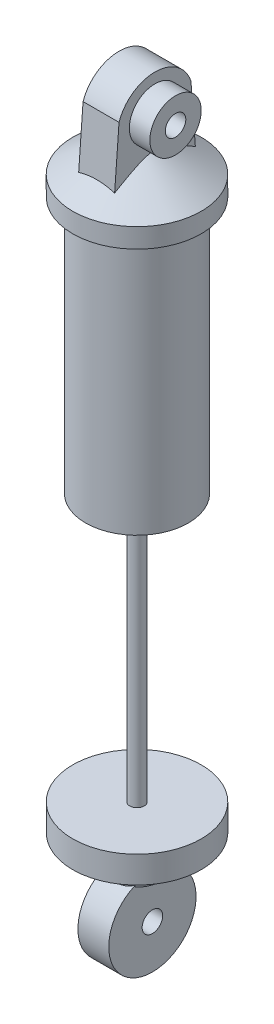
SolidWorks part; units mm, degrees
ref_plane "Front Plane" through (0, 0, 0) normal (0, 0, 1) x (1, 0, 0)
ref_plane "Top Plane" through (0, 0, 0) normal (0, 1, 0) x (1, 0, 0)
ref_plane "Right Plane" through (0, 0, 0) normal (1, 0, 0) x (0, 0, -1)
sketch "Sketch1" plane through (0, 0, 0) normal (0, 1, 0) x (1, 0, 0)
  circle A0 centre (0, 0) radius 7.9375
  dimension "D1" = 15.875
extrude "Extrude1" add sketch "Sketch1" against normal blind 70.485
ref_plane "Plane1" through (0, 3.937, 0) normal (0, 1, 0) x (-1, 0, 0)
sketch "Sketch3" plane through (0, 3.937, 0) normal (0, 1, 0) x (-1, 0, 0)
  circle A0 centre (0, 0) radius 1.905
  dimension "D1" = 3.81
loft "Loft1" add profiles "Sketch1<2>", "Sketch3" connector at (3.2072, 0, 7.2607) connector at (0.0754, 3.937, 1.9035)
sketch "Sketch1<2>" plane through (0, 0, 0) normal (0, 1, 0) x (1, 0, 0) same geometry as "Sketch1"
sketch "Sketch4" plane through (0, 0, 0) normal (1, 0, 0) x (0, 0, -1)
  line L0 (-4.9656, 1.905) -> (4.9656, 1.905) construction
  line L1 (4.9656, 1.905) -> (4.445, 8.89)
  line L2 (0, 12.065) -> (4.9656, 12.065) construction
  line L3 (-4.445, 8.89) -> (-4.9656, 1.905)
  line L4 (0, 0) -> (0, 9.4629) construction
  line L5 (-4.9656, 1.905) -> (-5.1076, 0)
  line L6 (7.9375, 0) -> (-7.9375, 0) construction
  line L7 (4.9656, 1.905) -> (5.1076, 0)
  line L8 (5.1076, 0) -> (-5.1076, 0)
  line L10 (-1.27, 6.35) -> (1.27, 6.35) construction
  line L11 (-1.27, 6.35) -> (-1.27, 8.89) construction
  line L12 (-1.27, 8.89) -> (1.27, 8.89) construction
  line L13 (1.27, 6.35) -> (1.27, 8.89) construction
  line L14 (-1.27, 6.35) -> (1.27, 8.89) construction
  line L15 (-1.27, 8.89) -> (1.27, 6.35) construction
  arc A0 (-4.445, 8.89) -> (4.445, 8.89) centre (0, 7.366) cw
  circle A1 centre (0, 7.62) radius 1.27
  spline S0 degree 3 poles (-1.905, 3.937) (-1.9298, 3.9193) (-1.963, 3.8954) (-2.003, 3.867) (-2.0531, 3.8315) (-2.1087, 3.7925) (-2.2033, 3.7265) (-2.2759, 3.6762) (-2.3922, 3.5963) (-2.475, 3.5398) (-2.579, 3.4693) (-2.6662, 3.4104) (-2.7586, 3.3483) (-2.8555, 3.2835) (-2.9745, 3.204) (-3.1326, 3.0991) (-3.37, 2.9424) (-3.5551, 2.8209) (-3.7198, 2.7132) (-3.826, 2.6438) (-3.9668, 2.552) (-4.1229, 2.4504) (-4.2648, 2.3583) (-4.3988, 2.2714) (-4.5561, 2.1695) (-4.7194, 2.0639) (-4.8575, 1.9747) (-5.0644, 1.8412) (-5.2722, 1.7074) (-5.5334, 1.5394) (-5.7601, 1.3937) (-6.0463, 1.21) (-6.4025, 0.9816) (-6.7879, 0.7348) (-7.1542, 0.5005) (-7.414, 0.3344) (-7.6599, 0.1773) (-7.8134, 0.0793) (-7.9375, 0) knots 0 0 0 0 0.012685 0.017018 0.020445 0.03826 0.045291 0.068488 0.075025 0.104079 0.110205 0.127331 0.14794 0.156552 0.175873 0.207562 0.235559 0.294302 0.299794 0.317492 0.347152 0.369783 0.395042 0.417599 0.436317 0.473091 0.498532 0.504794 0.575636 0.60146 0.634088 0.687922 0.743056 0.810289 0.878494 0.92414 0.938684 1 1 1 1 construction
  spline S1 degree 3 poles (7.9375, 0) (7.8257, 0.0714) (7.6722, 0.1694) (7.5036, 0.2772) (7.3066, 0.4031) (6.9555, 0.6275) (6.4286, 0.9648) (5.9657, 1.2616) (5.6639, 1.4555) (5.5129, 1.5525) (5.3908, 1.6311) (5.2417, 1.727) (5.0781, 1.8325) (4.9585, 1.9096) (4.8941, 1.9511) (4.7939, 2.0158) (4.633, 2.1197) (4.472, 2.224) (4.3176, 2.324) (4.1478, 2.4342) (3.9473, 2.5646) (3.7978, 2.6622) (3.7128, 2.7177) (3.6411, 2.7646) (3.5677, 2.8127) (3.4747, 2.8737) (3.3779, 2.9373) (3.2891, 2.9957) (3.2048, 3.0512) (3.1255, 3.1037) (3.0458, 3.1567) (2.9673, 3.2089) (2.8929, 3.2585) (2.8394, 3.2942) (2.7934, 3.325) (2.733, 3.3655) (2.6476, 3.4229) (2.5621, 3.4807) (2.4783, 3.5376) (2.4054, 3.5873) (2.336, 3.6349) (2.2544, 3.6911) (2.1808, 3.7421) (2.0885, 3.8066) (2.0336, 3.8453) (1.966, 3.8933) (1.932, 3.9177) (1.905, 3.937) knots 0 0 0 0 0.055193 0.075764 0.083269 0.152469 0.24918 0.343561 0.381249 0.39843 0.418269 0.441638 0.472216 0.499267 0.500879 0.504047 0.549312 0.580095 0.584151 0.625871 0.664303 0.683667 0.700174 0.706544 0.71932 0.736702 0.752813 0.767763 0.781713 0.794826 0.807252 0.822002 0.834734 0.844578 0.84877 0.857738 0.874872 0.891566 0.90071 0.917004 0.928262 0.935737 0.958237 0.965513 0.982582 0.986185 1 1 1 1 construction
  dimension "D5" = 2.54
  dimension "D1" = 1.905
  dimension "D2" = 8.89
  dimension "D3" = 6.985
  dimension "D4" = 3.175
  dimension "D6" = 3.175
extrude "Extrude2" add sketch "Sketch4" along normal mid plane 4.445
sketch "Sketch5" plane through (0, 0, 0) normal (1, 0, 0) x (0, 0, -1)
  line L0 (0, -70.485) -> (0, -84.455) construction
  line L1 (-7.9375, -70.485) -> (7.9375, -70.485) construction
  circle A0 centre (0, -79.0575) radius 5.3975
  circle A1 centre (0, -79.0575) radius 1.27
  dimension "D2" = 10.795
  dimension "D3" = 2.54
  dimension "D1" = 13.97
extrude "Extrude3" add sketch "Sketch5" along normal mid plane 3.81 separate body
sketch "Sketch6" plane through (0, -70.485, 0) normal (0, -1, 0) x (1, 0, 0)
  circle A0 centre (0, 0) radius 4.1275
  dimension "D1" = 8.255
extrude "Extrude4" add sketch "Sketch6" along normal blind 1.905
sketch "Sketch7" plane through (0, -72.39, 0) normal (0, -1, 0) x (1, 0, 0)
  circle A0 centre (0, 0) radius 2.8575
  dimension "D1" = 5.715
extrude "Extrude5" add sketch "Sketch7" along normal blind 1.905
sketch "Sketch8" plane through (2.2225, 0, 0) normal (1, 0, 0) x (0, 0, -1)
  circle A0 centre (0, 7.62) radius 3.175
  circle A1 centre (0, 7.62) radius 1.27
  circle A2 centre (0, 7.62) radius 1.27 construction
  dimension "D1" = 6.35
extrude "Extrude6" add sketch "Sketch8" along normal blind 2.54
ref_plane "Plane2" through (0, -2.413, 0) normal (0, 1, 0) x (-1, 0, 0)
sketch "Sketch9" plane through (0, -2.413, 0) normal (0, 1, 0) x (-1, 0, 0)
  circle A0 centre (0, 0) radius 6.35
  circle A1 centre (0, 0) radius 7.9375
  dimension "D1" = 12.7
  dimension "D2" = 15.875
extrude "Extrude7" cut sketch "Sketch9" against normal blind 33.02
ref_plane "Plane4" through (0, -34.163, 0) normal (0, 1, 0) x (-1, 0, 0)
sketch "Sketch10" plane through (0, -34.163, 0) normal (0, 1, 0) x (-1, 0, 0)
  circle A0 centre (0, 0) radius 0.889
  circle A1 centre (0, 0) radius 8.451
  dimension "D1" = 1.778
  dimension "D2" = 16.9021
extrude "Extrude8" cut sketch "Sketch10" against normal blind 33.02
